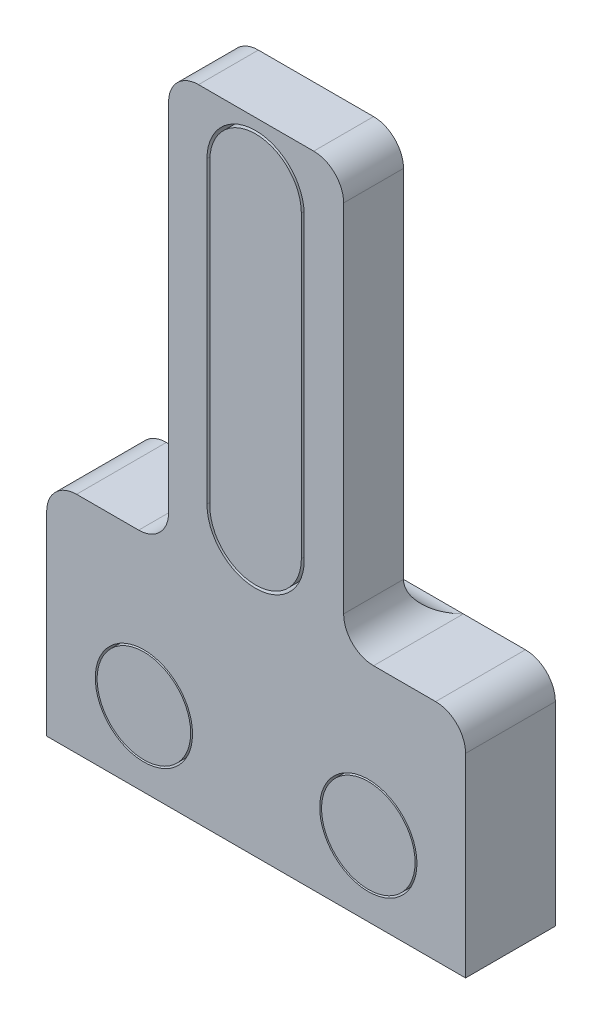
SolidWorks part; units mm, degrees
ref_plane "Front Plane" through (0, 0, 0) normal (0, 0, 1) x (1, 0, 0)
ref_plane "Top Plane" through (0, 0, 0) normal (0, 1, 0) x (1, 0, 0)
ref_plane "Right Plane" through (0, 0, 0) normal (1, 0, 0) x (0, 0, -1)
sketch "Sketch2" plane through (0, 0, 0) normal (0, 0, 1) x (1, 0, 0)
  line L1 (-28, 15) -> (0, 15)
  line L2 (-28, 15) -> (-28, 0)
  line L3 (-28, 0) -> (0, 0)
  line L4 (0, 15) -> (0, 0)
  dimension "D1" = 28
  dimension "D2" = 15
extrude "Boss-Extrude1" add sketch "Sketch2" along normal blind 6
sketch "Sketch3" plane through (0, 0, 6) normal (0, 0, 1) x (1, 0, 0)
  line L0 (-28, 15) -> (-28, 0) construction
  line L1 (0, 0) -> (0, 15) construction
  line L2 (0, 15) -> (-28, 15) construction
  circle A0 centre (-21.5, 5) radius 1.75
  circle A1 centre (-6.5, 5) radius 1.75
  dimension "D5" = 3.5
  dimension "D6" = 3.5
  dimension "D1" = 6.5
  dimension "D3" = 6.5
  dimension "D11" = 10
  dimension "D12" = 10
extrude "Cut-Extrude1" cut sketch "Sketch3" against normal through all both and the other way through all
sketch "Sketch6" plane through (0, 0, 6) normal (0, 0, 1) x (1, 0, 0)
  circle A0 centre (-21.5, 5) radius 3.25
  circle A1 centre (-6.5, 5) radius 3.25
  dimension "D1" = 6.5
  dimension "D2" = 6.5
extrude "Cut-Extrude2" cut sketch "Sketch6" against normal blind 3.5
sketch "Sketch7" plane through (0, 0, 0) normal (0, 0, -1) x (-1, 0, 0)
  line L0 (0, 15) -> (28, 15) construction
  line L1 (8.15, 15) -> (19.85, 15)
  line L2 (8.15, 15) -> (8.15, 42.7867)
  line L3 (8.15, 42.7867) -> (19.85, 42.7867)
  line L4 (19.85, 15) -> (19.85, 42.7867)
  line L5 (0, 0) -> (0, 15) construction
  dimension "D1" = 11.7
  dimension "D2" = 8.15
extrude "Boss-Extrude2" add sketch "Sketch7" against normal blind 6
sketch "Sketch8" plane through (0, 0, 0) normal (0, 0, -1) x (-1, 0, 0)
  line L0 (19.85, 15) -> (19.85, 42.7867) construction
  line L1 (8.15, 42.7867) -> (19.85, 42.7867)
  line L2 (8.15, 42.7867) -> (8.15, 15)
  line L3 (8.15, 15) -> (19.85, 15)
  line L4 (19.85, 42.7867) -> (19.85, 15)
extrude "Cut-Extrude3" cut sketch "Sketch8" against normal blind 2
fillet "Fillet1" radius 2 1 edges at (-14, 15, 2)
fillet "Fillet2" radius 2 1 edges at (-8.15, 15, 3)
fillet "Fillet3" radius 2 1 edges at (-19.85, 15, 3)
sketch "Sketch9" plane through (0, 0, 6) normal (0, 0, 1) x (1, 0, 0)
  line L0 (-14.0349, 38.7867) -> (-14.0349, 18.7867) construction
  line L1 (-12.2849, 38.7867) -> (-12.2849, 18.7867)
  line L2 (-15.7849, 38.7867) -> (-15.7849, 18.7867)
  line L3 (-19.85, 42.7867) -> (-8.15, 42.7867) construction
  arc A0 (-12.2849, 38.7867) -> (-15.7849, 38.7867) centre (-14.0349, 38.7867) ccw
  arc A1 (-15.7849, 18.7867) -> (-12.2849, 18.7867) centre (-14.0349, 18.7867) ccw
  point P2 (-14.0349, 28.7867)
  dimension "D1" = 3.5
  dimension "D2" = 20
  dimension "D3" = 4
extrude "Cut-Extrude4" cut sketch "Sketch9" against normal through all both and the other way through all
sketch "Sketch10" plane through (0, 0, 6) normal (0, 0, 1) x (1, 0, 0)
  line L0 (-14.0349, 38.7867) -> (-14.0349, 18.7867) construction
  line L1 (-10.7849, 38.7867) -> (-10.7849, 18.7867)
  line L2 (-17.2849, 38.7867) -> (-17.2849, 18.7867)
  arc A0 (-10.7849, 38.7867) -> (-17.2849, 38.7867) centre (-14.0349, 38.7867) ccw
  arc A1 (-17.2849, 18.7867) -> (-10.7849, 18.7867) centre (-14.0349, 18.7867) ccw
  point P4 (-14.0349, 28.7867)
  dimension "D1" = 6.5
extrude "Cut-Extrude5" cut sketch "Sketch10" against normal blind 2 and the other way through all
fillet "Fillet4" radius 2 2 edges at (-8.15, 42.7867, 4) (-19.85, 42.7867, 4)
fillet "Fillet5" radius 2 2 edges at (0, 15, 3) (-28, 15, 3)
sketch "Sketch11" plane through (0, 0, 6) normal (0, 0, 1) x (1, 0, 0)
  circle A0 centre (-21.5, 5) radius 3.125
  circle A1 centre (-6.5, 5) radius 3.125
  dimension "D1" = 6.25
  dimension "D2" = 6.25
extrude "Boss-Extrude3" add sketch "Sketch11" against normal blind 3.25 separate body
sketch "Sketch12" plane through (0, 0, 6) normal (0, 0, 1) x (1, 0, 0)
  line L0 (-14.0349, 38.7867) -> (-14.0349, 18.7867) construction
  line L1 (-10.9772, 38.7867) -> (-10.9772, 18.7867)
  line L2 (-17.0927, 38.7867) -> (-17.0927, 18.7867)
  arc A0 (-10.9772, 38.7867) -> (-17.0927, 38.7867) centre (-14.0349, 38.7867) ccw
  arc A1 (-17.0927, 18.7867) -> (-10.9772, 18.7867) centre (-14.0349, 18.7867) ccw
  point P4 (-14.0349, 28.7867)
extrude "Boss-Extrude4" add sketch "Sketch12" against normal blind 1.75
